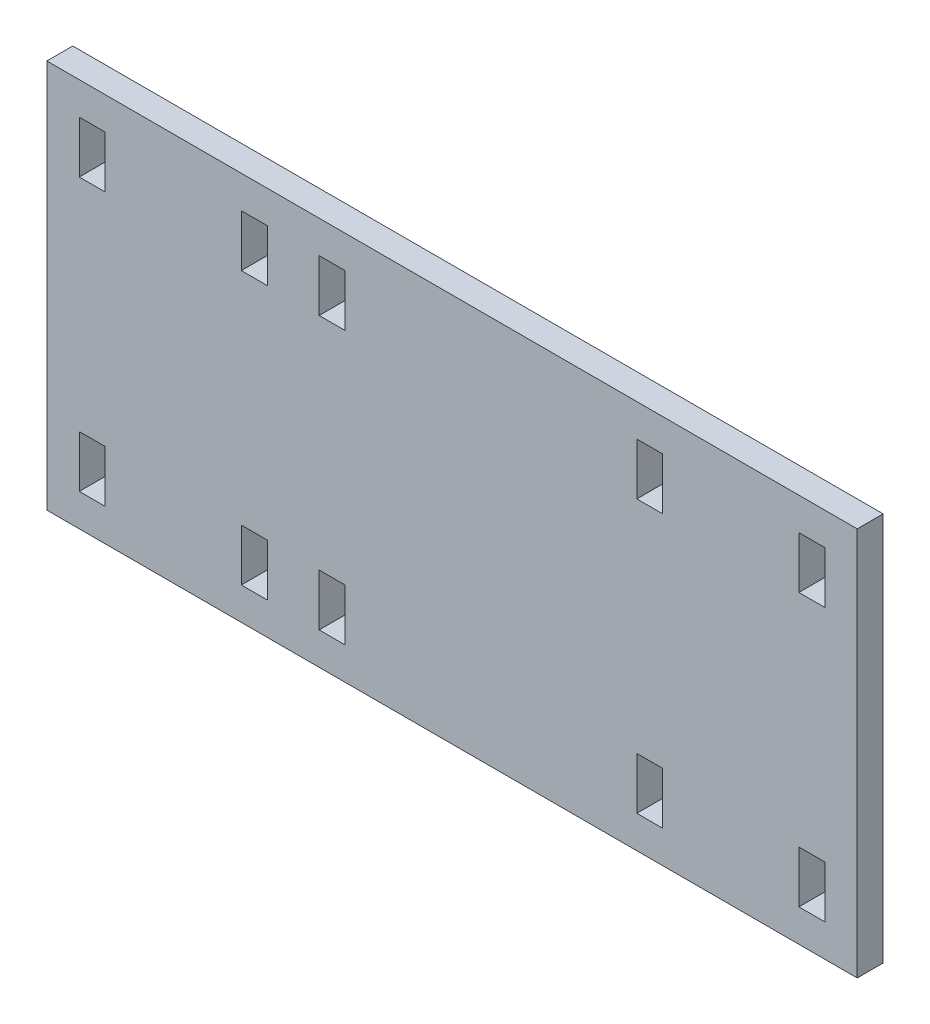
SolidWorks part; units mm, degrees
ref_plane "Front Plane" through (0, 0, 0) normal (0, 0, 1) x (1, 0, 0)
ref_plane "Top Plane" through (0, 0, 0) normal (0, 1, 0) x (1, 0, 0)
ref_plane "Right Plane" through (0, 0, 0) normal (1, 0, 0) x (0, 0, -1)
sketch "Sketch1" plane through (0, 0, 0) normal (0, 0, 1) x (1, 0, 0)
  line L0 (0, 66.0849) -> (0, -70.4198) construction
  line L6 (-38.5, 25) -> (-34.5, 25)
  line L7 (22.5, 25) -> (26.5, 25)
  line L8 (22.5, 25) -> (22.5, 17)
  line L9 (22.5, 17) -> (26.5, 17)
  line L10 (26.5, 25) -> (26.5, 17)
  line L11 (-103.5149, 0) -> (102.2922, 0) construction
  line L12 (22.5, -17) -> (26.5, -17)
  line L13 (22.5, -25) -> (22.5, -17)
  line L14 (26.5, -25) -> (26.5, -17)
  line L15 (22.5, -25) -> (26.5, -25)
  line L16 (-22.5, 25) -> (-26.5, 25)
  line L17 (-22.5, 25) -> (-22.5, 17)
  line L18 (-26.5, 25) -> (-26.5, 17)
  line L19 (-22.5, 17) -> (-26.5, 17)
  line L20 (-22.5, -17) -> (-26.5, -17)
  line L21 (-22.5, -25) -> (-22.5, -17)
  line L22 (-26.5, -25) -> (-26.5, -17)
  line L23 (-22.5, -25) -> (-26.5, -25)
  line L36 (56.5, 30) -> (56.5, -30)
  line L39 (47.5, 25) -> (51.5, 25)
  line L40 (47.5, 25) -> (47.5, 17)
  line L41 (47.5, 17) -> (51.5, 17)
  line L42 (51.5, 25) -> (51.5, 17)
  line L43 (47.5, -17) -> (51.5, -17)
  line L44 (47.5, -17) -> (47.5, -25)
  line L45 (47.5, -25) -> (51.5, -25)
  line L46 (51.5, -17) -> (51.5, -25)
  line L47 (-38.5, 25) -> (-38.5, 17)
  line L48 (-38.5, 17) -> (-34.5, 17)
  line L49 (-34.5, 25) -> (-34.5, 17)
  line L50 (-38.5, -17) -> (-34.5, -17)
  line L51 (-38.5, -17) -> (-38.5, -25)
  line L52 (-38.5, -25) -> (-34.5, -25)
  line L53 (-34.5, -17) -> (-34.5, -25)
  line L57 (-68.5, 30) -> (-68.5, -30)
  line L59 (-68.5, 30) -> (56.5, 30)
  line L60 (-63.5, 25) -> (-59.5, 25)
  line L61 (-63.5, 25) -> (-63.5, 17)
  line L62 (-63.5, 17) -> (-59.5, 17)
  line L63 (-59.5, 25) -> (-59.5, 17)
  line L64 (-63.5, -17) -> (-59.5, -17)
  line L65 (-63.5, -17) -> (-63.5, -25)
  line L66 (-63.5, -25) -> (-59.5, -25)
  line L67 (-59.5, -17) -> (-59.5, -25)
  line L68 (-68.5, -30) -> (56.5, -30)
  point P0 (0, 0)
  dimension "D2" = 60
  dimension "D3" = 8
  dimension "D5" = 4
  dimension "D6" = 8
  dimension "D7" = 45
  dimension "D8" = 21
  dimension "D9" = 21
  dimension "D10" = 5
  dimension "D12" = 5
extrude "Boss-Extrude1" add sketch "Sketch1" along normal blind 4
